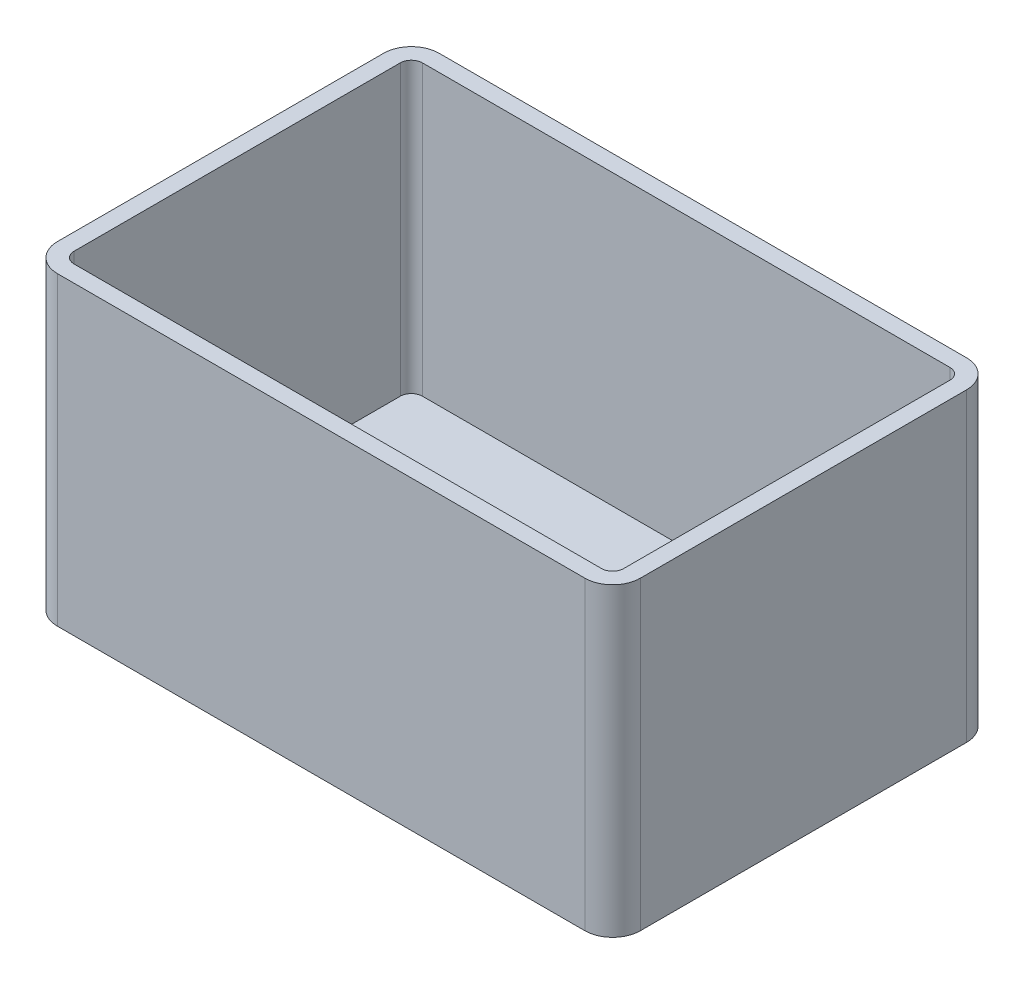
SolidWorks part; units mm, degrees
ref_plane "Front Plane" through (0, 0, 0) normal (0, 0, 1) x (1, 0, 0)
ref_plane "Top Plane" through (0, 0, 0) normal (0, 1, 0) x (1, 0, 0)
ref_plane "Right Plane" through (0, 0, 0) normal (1, 0, 0) x (0, 0, -1)
sketch "Sketch2" plane through (0, 0, 0) normal (0, 1, 0) x (1, 0, 0)
  line L1 (47.5, -34.375) -> (-47.5, -34.375)
  line L2 (52.5, -29.375) -> (52.5, 29.375)
  line L3 (47.5, 34.375) -> (-47.5, 34.375)
  line L4 (-52.5, -29.375) -> (-52.5, 29.375)
  arc A0 (-47.5, -34.375) -> (-52.5, -29.375) centre (-47.5, -29.375) cw
  arc A1 (47.5, -34.375) -> (52.5, -29.375) centre (47.5, -29.375) ccw
  arc A2 (52.5, 29.375) -> (47.5, 34.375) centre (47.5, 29.375) ccw
  arc A3 (-47.5, 34.375) -> (-52.5, 29.375) centre (-47.5, 29.375) ccw
  point P0 (0, 0)
  point P8 (-52.5, -34.375)
  point P13 (52.5, 34.375)
  point P16 (-52.5, 34.375)
  dimension "D3" = 5
  dimension "D1" = 105
  dimension "D2" = 68.75
extrude "Boss-Extrude1" add sketch "Sketch2" along normal blind 55
shell "Shell1" thickness 3 removed face at (0, 55, 0)
sketch "battery_connector_sketch" plane through (0, 3, 0) normal (0, 1, 0) x (1, 0, 0)
  line L0 (-43.2554, -24.8314) -> (-43.2554, -6.8814) construction
  line L1 (-48.2554, -4.8314) -> (-48.2554, -29.1314)
  line L2 (-46.2554, -31.1314) -> (-40.2554, -31.1314)
  line L3 (-40.2554, -2.8314) -> (-46.2554, -2.8314)
  line L4 (-39.5054, -13.4014) -> (-39.5054, -20.5614)
  line L5 (-38.2554, -4.8314) -> (-38.2554, -12.0614)
  line L6 (-38.2554, -29.1314) -> (-38.2554, -21.9014)
  line L7 (-38.2554, -12.0614) -> (-39.5054, -13.4014)
  line L8 (-38.2554, -21.9014) -> (-39.5054, -20.5614)
  line L9 (-41.26, -14.3503) -> (-45.2391, -14.3349)
  arc A0 (-38.2554, -4.8314) -> (-40.2554, -2.8314) centre (-40.2554, -4.8314) ccw
  arc A1 (-48.2554, -29.1314) -> (-46.2554, -31.1314) centre (-46.2554, -29.1314) ccw
  arc A2 (-40.2554, -31.1314) -> (-38.2554, -29.1314) centre (-40.2554, -29.1314) ccw
  arc A3 (-48.2554, -4.8314) -> (-46.2554, -2.8314) centre (-46.2554, -4.8314) cw
  circle A4 centre (-43.2554, -24.8314) radius 2.5
  circle A5 centre (-43.2554, -6.8814) radius 2.5
  arc A6 (-45.2391, -14.3349) -> (-41.26, -14.3503) centre (-43.2554, -15.8564) ccw
